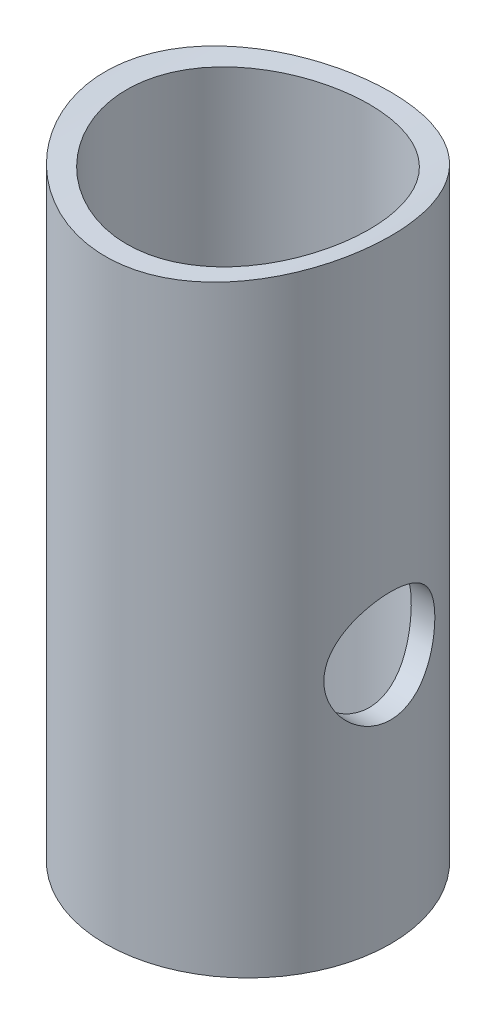
SolidWorks part; units mm, degrees
ref_plane "Front Plane" through (0, 0, 0) normal (0, 0, 1) x (1, 0, 0)
ref_plane "Top Plane" through (0, 0, 0) normal (0, 1, 0) x (1, 0, 0)
ref_plane "Right Plane" through (0, 0, 0) normal (1, 0, 0) x (0, 0, -1)
sketch "Sketch1" plane through (0, 0, 0) normal (0, 1, 0) x (1, 0, 0)
  circle A0 centre (0, 0) radius 57.15
  circle A1 centre (0, 0) radius 48.59
  dimension "D1" = 114.3
  dimension "D2" = 8.56
extrude "Boss-Extrude1" add sketch "Sketch1" along normal blind 245.75
sketch "Sketch2" plane through (0, 0, 0) normal (0, 0, 1) x (1, 0, 0)
  line L0 (57.15, 245.75) -> (-57.15, 245.75) construction
  line L1 (57.15, 245.75) -> (-57.15, 245.75)
  arc A0 (-57.15, 245.75) -> (57.15, 245.75) centre (0, 472.045) ccw
  point P4 (0, 245.75)
  dimension "D1" = 466.8
extrude "Cut-Extrude1" cut sketch "Sketch2" against normal mid plane 115.75
sketch "Sketch3" plane through (0, 0, 0) normal (1, 0, 0) x (0, 0, -1)
  circle A0 centre (0, 100) radius 22.25
  dimension "D1" = 44.5
  dimension "D2" = 100
extrude "Cut-Extrude2" cut sketch "Sketch3" along normal up to next
